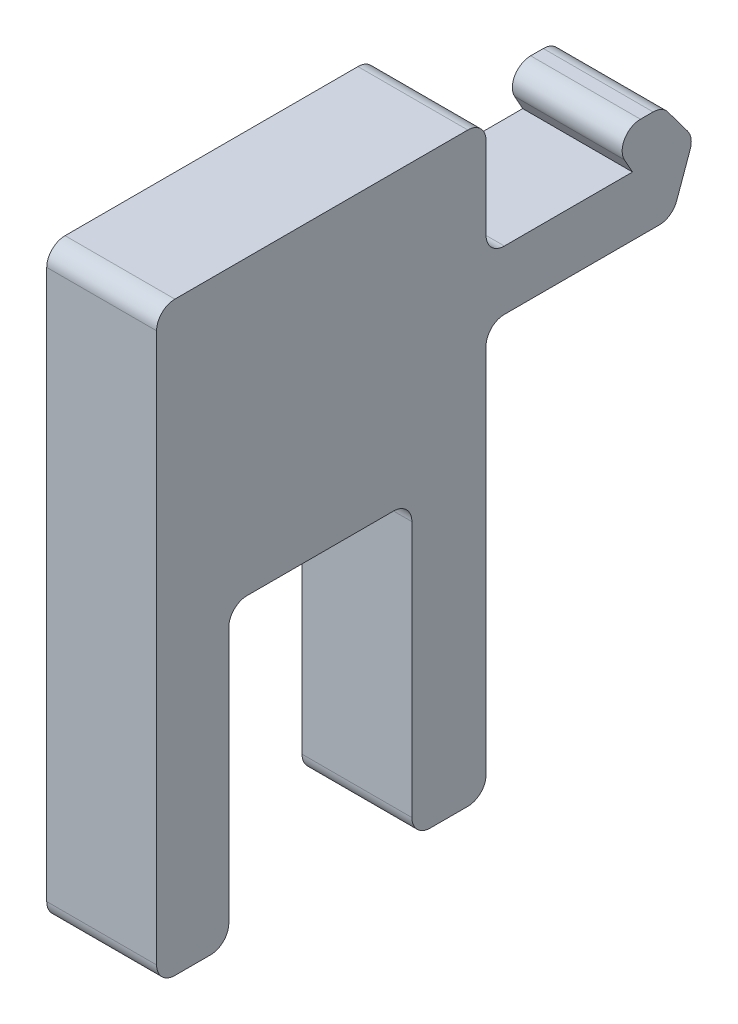
SolidWorks part; units mm, degrees
ref_plane "Alzado" through (0, 0, 0) normal (0, 0, 1) x (1, 0, 0)
ref_plane "Planta" through (0, 0, 0) normal (0, 1, 0) x (1, 0, 0)
ref_plane "Vista lateral" through (0, 0, 0) normal (1, 0, 0) x (0, 0, -1)
sketch "Croquis1" plane through (0, 0, 0) normal (1, 0, 0) x (0, 0, -1)
  line L1 (-4.4729, 8) -> (4.5271, 8)
  line L2 (-4.4729, 8) -> (-4.4729, -8)
  line L3 (-4.4729, -8) -> (4.5271, -8)
  line L16 (4.5271, 8) -> (4.5271, -8)
  dimension "D1" = 4.5271
  dimension "D2" = 8
  dimension "D3" = 16
  dimension "D4" = 9
extrude "Saliente-Extruir1" add sketch "Croquis1" along normal blind 3
sketch "Croquis2" plane through (3, 0, 0) normal (1, 0, 0) x (0, 0, -1)
  line L0 (0, 0) -> (0, -9.3656) construction
  line L1 (-4.4729, -8) -> (4.5271, -8) construction
  line L2 (-2.5, -8) -> (2.5, -8)
  line L3 (-2.5, -8) -> (-2.5, 0)
  line L4 (-2.5, 0) -> (2.5, 0)
  line L5 (2.5, -8) -> (2.5, 0)
  dimension "D1" = 2.5
  dimension "D2" = 2.5
  dimension "D3" = 8
extrude "Cortar-Extruir1" cut sketch "Croquis2" against normal up to surface (3 mm away) up to face at (0, 0, -0.0271)
sketch "Croquis4" plane through (3, 0, 0) normal (1, 0, 0) x (0, 0, -1)
  line L0 (4.5271, 4.7559) -> (8.5271, 4.7559)
  line L2 (4.5271, -8) -> (4.5271, 8) construction
  line L9 (2.5, 0) -> (-2.5, 0) construction
  line L10 (0, 0) -> (0, 10.8389) construction
  line L11 (8.5271, 4.7559) -> (7.896, 5.8963)
  line L12 (7.896, 5.8963) -> (9.3404, 5.8963)
  line L13 (9.3404, 5.8963) -> (10.1928, 4.7559)
  line L14 (10.1928, 4.7559) -> (9.6127, 3.1377)
  line L15 (9.6127, 3.1377) -> (4.5271, 3.1377)
  line L16 (4.5271, 4.7559) -> (4.5271, 3.1377)
  dimension "D1" = 3.1377
  dimension "D2" = 4.7559
  dimension "D3" = 5.8963
  dimension "D4" = 4
extrude "Saliente-Extruir2" add sketch "Croquis4" against normal up to surface (3 mm away) up to face at (0, -2, -0.0135)
fillet "Redondeo2" radius 0.5 14 edges at (1.5, 5.8963, -7.896) (1.5, 5.8963, -9.3404) (1.5, 4.7559, -10.1928) (1.5, 3.1377, -4.5271) (1.5, 3.1377, -9.6127) (1.5, 4.7559, -4.5271) (1.5, 8, -4.5271) (1.5, 8, 4.4729) (1.5, 0, 2.5) (1.5, 0, -2.5) (1.5, -8, 4.4729) (1.5, -8, -2.5) (1.5, -8, -4.5271) (1.5, -8, 2.5)
